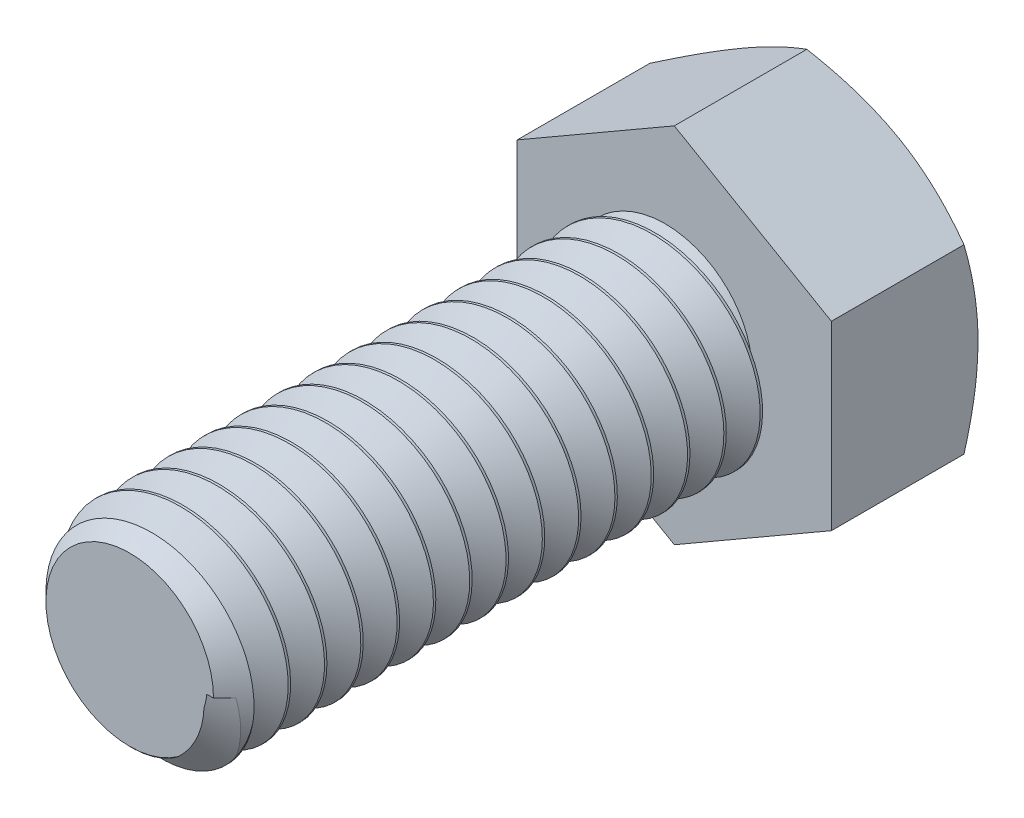
SolidWorks part; units mm, degrees
ref_plane "Front Plane" through (0, 0, 0) normal (0, 0, 1) x (1, 0, 0)
ref_plane "Top Plane" through (0, 0, 0) normal (0, 1, 0) x (1, 0, 0)
ref_plane "Right Plane" through (0, 0, 0) normal (1, 0, 0) x (0, 0, -1)
sketch "Sketch1" plane through (0, 0, 0) normal (0, 0, 1) x (1, 0, 0)
  line L1 (7.5, -4.3301) -> (7.5, 4.3301)
  line L2 (7.5, 4.3301) -> (0, 8.6603)
  line L3 (0, 8.6603) -> (-7.5, 4.3301)
  line L4 (-7.5, 4.3301) -> (-7.5, -4.3301)
  line L5 (-7.5, -4.3301) -> (0, -8.6603)
  line L6 (0, -8.6603) -> (7.5, -4.3301)
  circle A0 centre (0, 0) radius 7.5 construction
  dimension "D2" = 15
extrude "Boss-Extrude1" add sketch "Sketch1" along normal blind 7
sketch "Sketch2" plane through (0, 0, 0) normal (0, 0, -1) x (-1, 0, 0)
  circle A0 centre (0, 0) radius 7.5
extrude "Cut-Extrude2" cut sketch "Sketch2" against normal blind 5 draft 60 flip side to cut
sketch "Sketch3" plane through (0, 0, 7) normal (0, 0, 1) x (1, 0, 0)
  circle A0 centre (0, 0) radius 5
  dimension "D1" = 10
extrude "Boss-Extrude2" add sketch "Sketch3" along normal blind 26
chamfer "Chamfer1" distance 1 angle 45 1 edges at (5, 0, 33)
sketch "Sketch4" plane through (0, 0, 33) normal (0, 0, 1) x (1, 0, 0)
  circle A0 centre (0, 0) radius 5
  dimension "D1" = 10
curve "Helix/Spiral1" pitch 1.7333 height 26 turns 15
sketch "Sketch5" plane through (0, 0, 0) normal (0, 1, 0) x (1, 0, 0)
  line L1 (5.7427, -34.1867) -> (5.6564, -31.7634)
  line L2 (5.6564, -31.7634) -> (3.6009, -33.0499)
  line L3 (3.6009, -33.0499) -> (5.7427, -34.1867)
  circle A0 centre (5, -33) radius 0.7 construction
  spline S0 degree 3 poles (5, -33) (5, -32.9641) (4.7397, -32.8916) (3.6276, -32.7834) (1.9632, -32.675) (0, -32.5667) (-1.9632, -32.4583) (-3.6276, -32.35) (-4.7397, -32.2417) (-5.1302, -32.1333) (-4.7397, -32.025) (-3.6276, -31.9167) (-1.9632, -31.8083) (0, -31.7) (1.9632, -31.5917) (3.6276, -31.4833) (4.7397, -31.375) (5.1302, -31.2667) (4.7397, -31.1583) (3.6276, -31.05) (1.9632, -30.9417) (0, -30.8333) (-1.9632, -30.725) (-3.6276, -30.6167) (-4.7397, -30.5083) (-5.1302, -30.4) (-4.7397, -30.2917) (-3.6276, -30.1833) (-1.9632, -30.075) (0, -29.9667) (1.9632, -29.8583) (3.6276, -29.75) (4.7397, -29.6417) (5.1302, -29.5333) (4.7397, -29.425) (3.6276, -29.3167) (1.9632, -29.2083) (0, -29.1) (-1.9632, -28.9917) (-3.6276, -28.8833) (-4.7397, -28.775) (-5.1302, -28.6667) (-4.7397, -28.5583) (-3.6276, -28.45) (-1.9632, -28.3417) (0, -28.2333) (1.9632, -28.125) (3.6276, -28.0167) (4.7397, -27.9083) (5.1302, -27.8) (4.7397, -27.6917) (3.6276, -27.5833) (1.9632, -27.475) (0, -27.3667) (-1.9632, -27.2583) (-3.6276, -27.15) (-4.7397, -27.0417) (-5.1302, -26.9333) (-4.7397, -26.825) (-3.6276, -26.7167) (-1.9632, -26.6083) (0, -26.5) (1.9632, -26.3917) (3.6276, -26.2833) (4.7397, -26.175) (5.1302, -26.0667) (4.7397, -25.9583) (3.6276, -25.85) (1.9632, -25.7417) (0, -25.6333) (-1.9632, -25.525) (-3.6276, -25.4167) (-4.7397, -25.3083) (-5.1302, -25.2) (-4.7397, -25.0917) (-3.6276, -24.9833) (-1.9632, -24.875) (0, -24.7667) (1.9632, -24.6583) (3.6276, -24.55) (4.7397, -24.4417) (5.1302, -24.3333) (4.7397, -24.225) (3.6276, -24.1167) (1.9632, -24.0083) (0, -23.9) (-1.9632, -23.7917) (-3.6276, -23.6833) (-4.7397, -23.575) (-5.1302, -23.4667) (-4.7397, -23.3583) (-3.6276, -23.25) (-1.9632, -23.1417) (0, -23.0333) (1.9632, -22.925) (3.6276, -22.8167) (4.7397, -22.7083) (5.1302, -22.6) (4.7397, -22.4917) (3.6276, -22.3833) (1.9632, -22.275) (0, -22.1667) (-1.9632, -22.0583) (-3.6276, -21.95) (-4.7397, -21.8417) (-5.1302, -21.7333) (-4.7397, -21.625) (-3.6276, -21.5167) (-1.9632, -21.4083) (0, -21.3) (1.9632, -21.1917) (3.6276, -21.0833) (4.7397, -20.975) (5.1302, -20.8667) (4.7397, -20.7583) (3.6276, -20.65) (1.9632, -20.5417) (0, -20.4333) (-1.9632, -20.325) (-3.6276, -20.2167) (-4.7397, -20.1083) (-5.1302, -20) (-4.7397, -19.8917) (-3.6276, -19.7833) (-1.9632, -19.675) (0, -19.5667) (1.9632, -19.4583) (3.6276, -19.35) (4.7397, -19.2417) (5.1302, -19.1333) (4.7397, -19.025) (3.6276, -18.9167) (1.9632, -18.8083) (0, -18.7) (-1.9632, -18.5917) (-3.6276, -18.4833) (-4.7397, -18.375) (-5.1302, -18.2667) (-4.7397, -18.1583) (-3.6276, -18.05) (-1.9632, -17.9417) (0, -17.8333) (1.9632, -17.725) (3.6276, -17.6167) (4.7397, -17.5083) (5.1302, -17.4) (4.7397, -17.2917) (3.6276, -17.1833) (1.9632, -17.075) (0, -16.9667) (-1.9632, -16.8583) (-3.6276, -16.75) (-4.7397, -16.6417) (-5.1302, -16.5333) (-4.7397, -16.425) (-3.6276, -16.3167) (-1.9632, -16.2083) (0, -16.1) (1.9632, -15.9917) (3.6276, -15.8833) (4.7397, -15.775) (5.1302, -15.6667) (4.7397, -15.5583) (3.6276, -15.45) (1.9632, -15.3417) (0, -15.2333) (-1.9632, -15.125) (-3.6276, -15.0167) (-4.7397, -14.9083) (-5.1302, -14.8) (-4.7397, -14.6917) (-3.6276, -14.5833) (-1.9632, -14.475) (0, -14.3667) (1.9632, -14.2583) (3.6276, -14.15) (4.7397, -14.0417) (5.1302, -13.9333) (4.7397, -13.825) (3.6276, -13.7167) (1.9632, -13.6083) (0, -13.5) (-1.9632, -13.3917) (-3.6276, -13.2833) (-4.7397, -13.175) (-5.1302, -13.0667) (-4.7397, -12.9583) (-3.6276, -12.85) (-1.9632, -12.7417) (0, -12.6333) (1.9632, -12.525) (3.6276, -12.4167) (4.7397, -12.3083) (5.1302, -12.2) (4.7397, -12.0917) (3.6276, -11.9833) (1.9632, -11.875) (0, -11.7667) (-1.9632, -11.6583) (-3.6276, -11.55) (-4.7397, -11.4417) (-5.1302, -11.3333) (-4.7397, -11.225) (-3.6276, -11.1167) (-1.9632, -11.0083) (0, -10.9) (1.9632, -10.7917) (3.6276, -10.6833) (4.7397, -10.575) (5.1302, -10.4667) (4.7397, -10.3583) (3.6276, -10.25) (1.9632, -10.1417) (0, -10.0333) (-1.9632, -9.925) (-3.6276, -9.8167) (-4.7397, -9.7083) (-5.1302, -9.6) (-4.7397, -9.4917) (-3.6276, -9.3833) (-1.9632, -9.275) (0, -9.1667) (1.9632, -9.0583) (3.6276, -8.95) (4.7397, -8.8417) (5.1302, -8.7333) (4.7397, -8.625) (3.6276, -8.5167) (1.9632, -8.4083) (0, -8.3) (-1.9632, -8.1917) (-3.6276, -8.0833) (-4.7397, -7.975) (-5.1302, -7.8667) (-4.7397, -7.7583) (-3.6276, -7.65) (-1.9632, -7.5417) (0, -7.4333) (1.9632, -7.325) (3.6276, -7.2166) (4.7397, -7.1084) (5, -7.0359) (5, -7) knots 0 0 0 0 0.004167 0.008333 0.0125 0.016667 0.020833 0.025 0.029167 0.033333 0.0375 0.041667 0.045833 0.05 0.054167 0.058333 0.0625 0.066667 0.070833 0.075 0.079167 0.083333 0.0875 0.091667 0.095833 0.1 0.104167 0.108333 0.1125 0.116667 0.120833 0.125 0.129167 0.133333 0.1375 0.141667 0.145833 0.15 0.154167 0.158333 0.1625 0.166667 0.170833 0.175 0.179167 0.183333 0.1875 0.191667 0.195833 0.2 0.204167 0.208333 0.2125 0.216667 0.220833 0.225 0.229167 0.233333 0.2375 0.241667 0.245833 0.25 0.254167 0.258333 0.2625 0.266667 0.270833 0.275 0.279167 0.283333 0.2875 0.291667 0.295833 0.3 0.304167 0.308333 0.3125 0.316667 0.320833 0.325 0.329167 0.333333 0.3375 0.341667 0.345833 0.35 0.354167 0.358333 0.3625 0.366667 0.370833 0.375 0.379167 0.383333 0.3875 0.391667 0.395833 0.4 0.404167 0.408333 0.4125 0.416667 0.420833 0.425 0.429167 0.433333 0.4375 0.441667 0.445833 0.45 0.454167 0.458333 0.4625 0.466667 0.470833 0.475 0.479167 0.483333 0.4875 0.491667 0.495833 0.5 0.504167 0.508333 0.5125 0.516667 0.520833 0.525 0.529167 0.533333 0.5375 0.541667 0.545833 0.55 0.554167 0.558333 0.5625 0.566667 0.570833 0.575 0.579167 0.583333 0.5875 0.591667 0.595833 0.6 0.604167 0.608333 0.6125 0.616667 0.620833 0.625 0.629167 0.633333 0.6375 0.641667 0.645833 0.65 0.654167 0.658333 0.6625 0.666667 0.670833 0.675 0.679167 0.683333 0.6875 0.691667 0.695833 0.7 0.704167 0.708333 0.7125 0.716667 0.720833 0.725 0.729167 0.733333 0.7375 0.741667 0.745833 0.75 0.754167 0.758333 0.7625 0.766667 0.770833 0.775 0.779167 0.783333 0.7875 0.791667 0.795833 0.8 0.804167 0.808333 0.8125 0.816667 0.820833 0.825 0.829167 0.833333 0.8375 0.841667 0.845833 0.85 0.854167 0.858333 0.8625 0.866667 0.870833 0.875 0.879167 0.883333 0.8875 0.891667 0.895833 0.9 0.904167 0.908333 0.9125 0.916667 0.920833 0.925 0.929167 0.933333 0.9375 0.941667 0.945833 0.95 0.954167 0.958333 0.9625 0.966667 0.970833 0.975 0.979167 0.983333 0.9875 0.991667 0.995833 1 1 1 1 construction
sweep "Cut-Sweep1" cut profiles "Sketch5" path "Helix/Spiral1"
